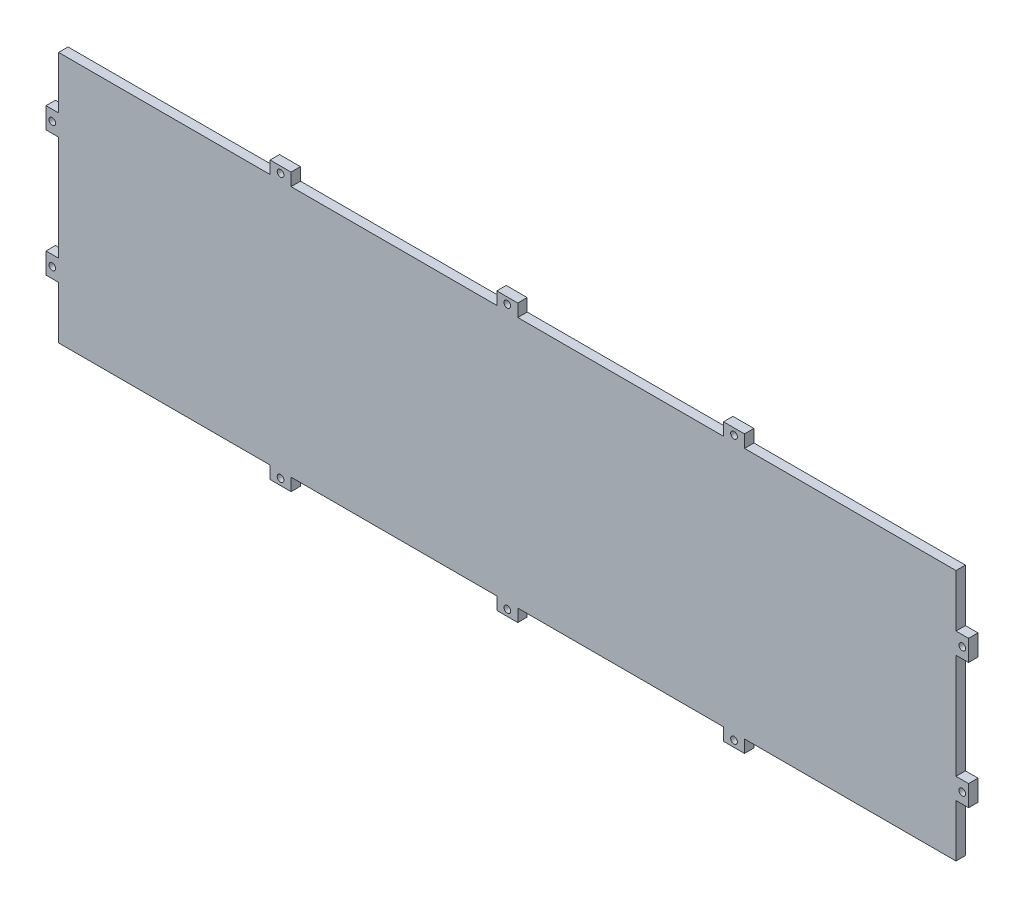
SolidWorks part; units mm, degrees
ref_plane "Front Plane" through (0, 0, 0) normal (0, 0, 1) x (1, 0, 0)
ref_plane "Top Plane" through (0, 0, 0) normal (0, 1, 0) x (1, 0, 0)
ref_plane "Right Plane" through (0, 0, 0) normal (1, 0, 0) x (0, 0, -1)
sketch "Sketch1" plane through (0, 0, 0) normal (0, 0, 1) x (1, 0, 0)
  line L0 (110.275, 127) -> (113.475, 127) construction
  line L1 (6, 250) -> (106.875, 250)
  line L2 (6, 250) -> (6, 225)
  line L3 (6, 130) -> (106.875, 130)
  line L4 (434, 250) -> (434, 225)
  line L5 (110.275, 130) -> (110.275, 124) construction
  line L6 (113.475, 124) -> (113.475, 130) construction
  line L7 (218.4, 127) -> (221.6, 127) construction
  line L8 (218.4, 130) -> (218.4, 124) construction
  line L9 (221.6, 124) -> (221.6, 130) construction
  line L10 (326.525, 127) -> (329.725, 127) construction
  line L11 (326.525, 130) -> (326.525, 124) construction
  line L12 (329.725, 124) -> (329.725, 130) construction
  line L13 (116.875, 130) -> (215, 130)
  line L14 (106.875, 124) -> (116.875, 124)
  line L15 (106.875, 124) -> (106.875, 130)
  line L16 (225, 130) -> (323.125, 130)
  line L17 (116.875, 124) -> (116.875, 130)
  line L18 (106.875, 124) -> (116.875, 130) construction
  line L19 (106.875, 130) -> (116.875, 124) construction
  line L20 (215, 124) -> (225, 124)
  line L21 (215, 124) -> (215, 130)
  line L22 (333.125, 130) -> (434, 130)
  line L23 (225, 124) -> (225, 130)
  line L24 (215, 124) -> (225, 130) construction
  line L25 (215, 130) -> (225, 124) construction
  line L26 (323.125, 124) -> (333.125, 124)
  line L27 (323.125, 124) -> (323.125, 130)
  line L28 (6, 190) -> (434, 190) construction
  line L29 (333.125, 124) -> (333.125, 130)
  line L30 (323.125, 124) -> (333.125, 130) construction
  line L31 (323.125, 130) -> (333.125, 124) construction
  line L32 (323.125, 256) -> (323.125, 250)
  line L33 (323.125, 256) -> (333.125, 256)
  line L34 (333.125, 256) -> (333.125, 250)
  line L35 (215, 256) -> (215, 250)
  line L36 (215, 256) -> (225, 256)
  line L37 (225, 256) -> (225, 250)
  line L38 (106.875, 256) -> (106.875, 250)
  line L39 (116.875, 256) -> (116.875, 250)
  line L40 (106.875, 256) -> (116.875, 256)
  line L41 (333.125, 250) -> (434, 250)
  line L42 (225, 250) -> (323.125, 250)
  line L43 (116.875, 250) -> (215, 250)
  line L44 (0, 250) -> (6, 190) construction
  line L45 (6, 215) -> (6, 165)
  line L46 (0, 215) -> (6, 215)
  line L47 (0, 215) -> (0, 225)
  line L48 (0, 225) -> (6, 225)
  line L49 (0, 250) -> (0, 225) construction
  line L50 (0, 215) -> (6, 225) construction
  line L51 (0, 225) -> (6, 215) construction
  line L52 (0, 155) -> (6, 155)
  line L53 (0, 165) -> (0, 155)
  line L54 (0, 165) -> (6, 165)
  line L55 (220, 190) -> (220, 221.6948) construction
  line L56 (440, 165) -> (434, 165)
  line L57 (440, 165) -> (440, 155)
  line L58 (440, 155) -> (434, 155)
  line L59 (440, 215) -> (434, 215)
  line L60 (440, 215) -> (440, 225)
  line L61 (440, 225) -> (434, 225)
  line L62 (6, 155) -> (6, 130)
  line L63 (434, 155) -> (434, 130)
  line L64 (434, 215) -> (434, 165)
  circle A0 centre (111.875, 127) radius 1.6
  circle A1 centre (220, 127) radius 1.6
  circle A2 centre (328.125, 127) radius 1.6
  circle A3 centre (328.125, 253) radius 1.6
  circle A4 centre (220, 253) radius 1.6
  circle A5 centre (111.875, 253) radius 1.6
  circle A6 centre (3, 220) radius 1.6
  circle A7 centre (3, 160) radius 1.6
  circle A8 centre (437, 220) radius 1.6
  circle A9 centre (437, 160) radius 1.6
  point P24 (111.875, 127)
  point P29 (220, 127)
  point P34 (328.125, 127)
  point P47 (106.875, 127)
  point P66 (106.875, 253)
  point P68 (3, 220)
  dimension "D3" = 3.2
  dimension "D1" = 10
  dimension "D2" = 10
extrude "Boss-Extrude1" add sketch "Sketch1" against normal blind 4.5
